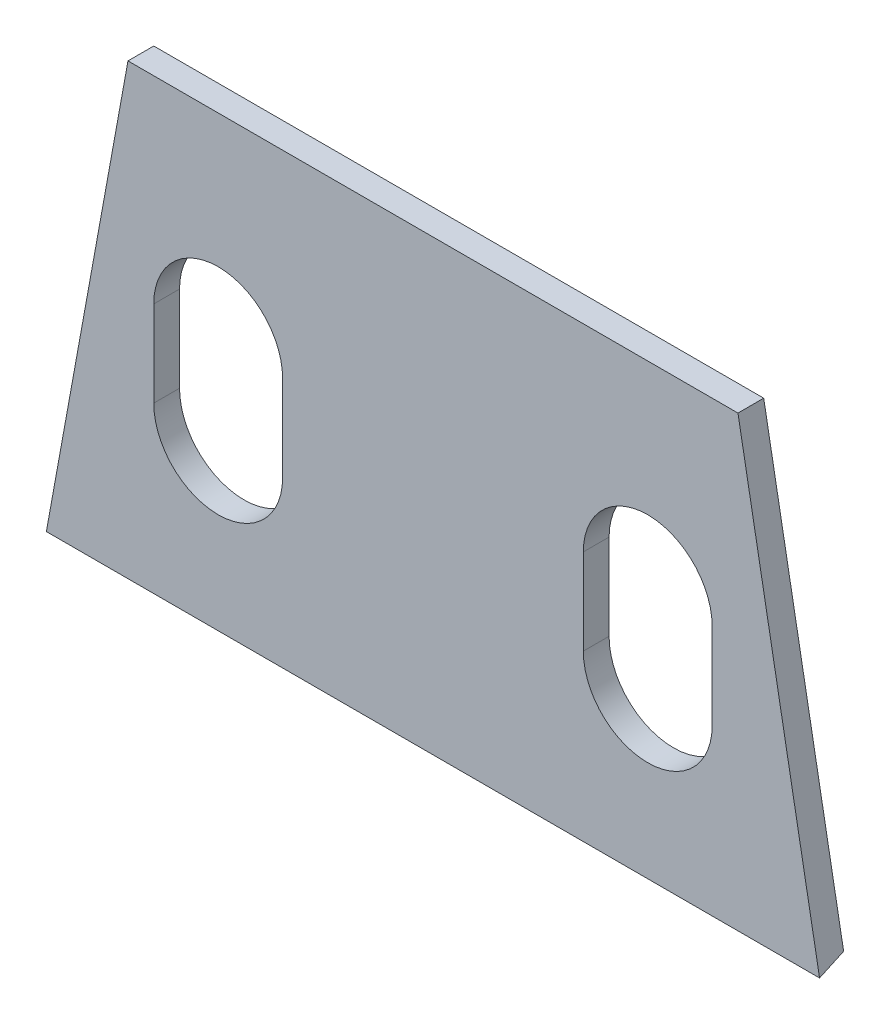
SolidWorks part; units mm, degrees
material "Acrylic (Medium-high impact)"
ref_plane "Front Plane" through (0, 0, 0) normal (0, 0, 1) x (1, 0, 0)
ref_plane "Top Plane" through (0, 0, 0) normal (0, 1, 0) x (1, 0, 0)
ref_plane "Right Plane" through (0, 0, 0) normal (1, 0, 0) x (0, 0, -1)
sketch "Sketch1" plane through (0, 0, 0) normal (0, 0, 1) x (1, 0, 0)
  line L0 (-45, 0) -> (45, 0)
  line L1 (-45, 0) -> (-35.5, 52.2)
  line L2 (-35.5, 52.2) -> (35.5, 52.2)
  line L3 (35.5, 52.2) -> (45, 0)
  point P0 (0, 52.2)
  point P4 (0, 0)
  dimension "D1" = 90
  dimension "D2" = 52.2
  dimension "D3" = 71
extrude "Boss-Extrude1" add sketch "Sketch1" along normal mid plane 3
sketch "Sketch2" plane through (0, 0, 1.5) normal (0, 0, 1) x (1, 0, 0)
  line L0 (-25, 29.2) -> (-25, 19.2) construction
  line L1 (-17.5, 29.2) -> (-17.5, 19.2)
  line L2 (-32.5, 29.2) -> (-32.5, 19.2)
  line L3 (0, 0) -> (0, 52.2) construction
  line L4 (-45, 0) -> (45, 0) construction
  line L5 (35.5, 52.2) -> (-35.5, 52.2) construction
  line L6 (25, 29.2) -> (25, 19.2) construction
  line L7 (17.5, 29.2) -> (17.5, 19.2)
  line L8 (32.5, 29.2) -> (32.5, 19.2)
  arc A0 (-17.5, 29.2) -> (-32.5, 29.2) centre (-25, 29.2) ccw
  arc A1 (-32.5, 19.2) -> (-17.5, 19.2) centre (-25, 19.2) ccw
  arc A2 (17.5, 29.2) -> (32.5, 29.2) centre (25, 29.2) cw
  arc A3 (32.5, 19.2) -> (17.5, 19.2) centre (25, 19.2) cw
  point P2 (-25, 24.2)
  point P15 (25, 24.2)
  dimension "D1" = 15
  dimension "D2" = 50
  dimension "D3" = 28
  dimension "D4" = 10
extrude "Cut-Extrude1" cut sketch "Sketch2" against normal through all
chamfer "Chamfer1" distance 3 angle 20 1 edges at (0, 0, -1.5) first distance on face at (0, 0, 0)
